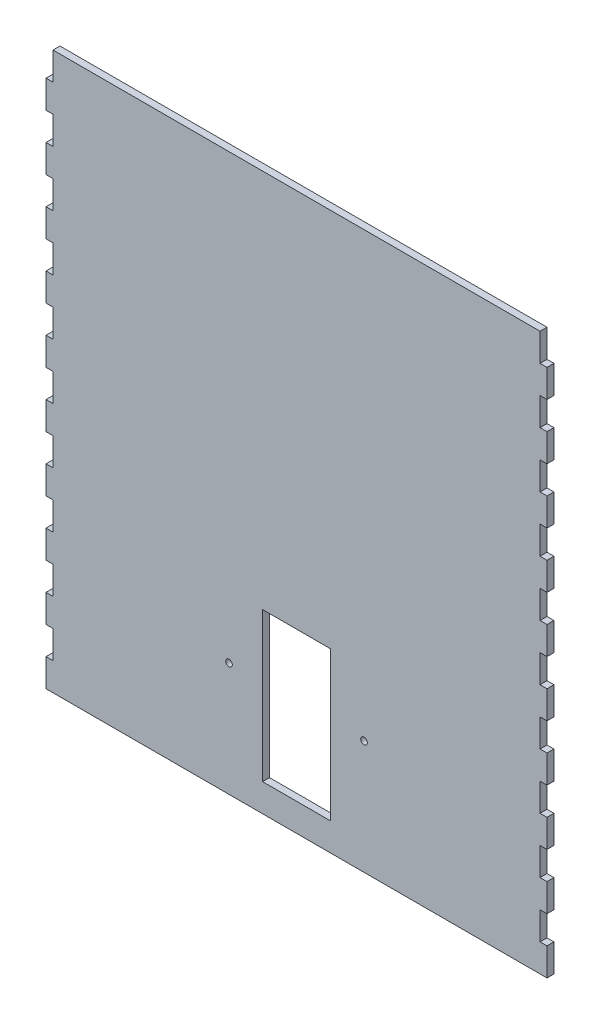
SolidWorks part; units mm, degrees
material "Acrylic (Medium-high impact)"
ref_plane "Front Plane" through (0, 0, 0) normal (0, 0, 1) x (1, 0, 0)
ref_plane "Top Plane" through (0, 0, 0) normal (0, 1, 0) x (1, 0, 0)
ref_plane "Right Plane" through (0, 0, 0) normal (1, 0, 0) x (0, 0, -1)
sketch "Sketch1" plane through (0, 0, 0) normal (0, 0, 1) x (1, 0, 0)
  line L0 (-114.3, 114.3) -> (-111.125, 114.3)
  line L1 (-114.3, 127) -> (114.3, 127)
  line L2 (-114.3, 127) -> (-114.3, -127)
  line L3 (-114.3, -127) -> (114.3, -127)
  line L4 (114.3, 127) -> (114.3, -127)
  line L5 (-114.3, 127) -> (-111.125, 127)
  line L6 (-114.3, 127) -> (-114.3, 114.3)
  line L7 (-114.3, 114.3) -> (-111.125, 114.3)
  line L8 (-111.125, 127) -> (-111.125, 114.3)
  line L9 (-114.3, 114.3) -> (-114.3, 101.6)
  line L10 (-114.3, 101.6) -> (-111.125, 101.6)
  line L11 (-111.125, 114.3) -> (-111.125, 101.6)
  line L12 (-114.3, 101.6) -> (-111.125, 101.6)
  line L13 (-114.3, 101.6) -> (-114.3, 88.9)
  line L14 (-114.3, 88.9) -> (-111.125, 88.9)
  line L15 (-111.125, 101.6) -> (-111.125, 88.9)
  line L16 (-114.3, 88.9) -> (-111.125, 88.9)
  line L17 (-114.3, 88.9) -> (-114.3, 76.2)
  line L18 (-114.3, 76.2) -> (-111.125, 76.2)
  line L19 (-111.125, 88.9) -> (-111.125, 76.2)
  line L20 (-114.3, 76.2) -> (-111.125, 76.2)
  line L21 (-114.3, 76.2) -> (-114.3, 63.5)
  line L22 (-114.3, 63.5) -> (-111.125, 63.5)
  line L23 (-111.125, 76.2) -> (-111.125, 63.5)
  line L24 (-114.3, 63.5) -> (-111.125, 63.5)
  line L25 (-114.3, 63.5) -> (-114.3, 50.8)
  line L26 (-114.3, 50.8) -> (-111.125, 50.8)
  line L27 (-111.125, 63.5) -> (-111.125, 50.8)
  line L28 (-114.3, 50.8) -> (-111.125, 50.8)
  line L29 (-114.3, 50.8) -> (-114.3, 38.1)
  line L30 (-114.3, 38.1) -> (-111.125, 38.1)
  line L31 (-111.125, 50.8) -> (-111.125, 38.1)
  line L32 (-114.3, 38.1) -> (-111.125, 38.1)
  line L33 (-114.3, 38.1) -> (-114.3, 25.4)
  line L34 (-114.3, 25.4) -> (-111.125, 25.4)
  line L35 (-111.125, 38.1) -> (-111.125, 25.4)
  line L36 (-114.3, 25.4) -> (-111.125, 25.4)
  line L37 (-114.3, 25.4) -> (-114.3, 12.7)
  line L38 (-114.3, 12.7) -> (-111.125, 12.7)
  line L39 (-111.125, 25.4) -> (-111.125, 12.7)
  line L40 (-114.3, 12.7) -> (-111.125, 12.7)
  line L41 (-114.3, 12.7) -> (-114.3, 0)
  line L42 (-114.3, 0) -> (-111.125, 0)
  line L43 (-111.125, 12.7) -> (-111.125, 0)
  line L44 (-114.3, 0) -> (-111.125, 0)
  line L45 (-114.3, 0) -> (-114.3, -12.7)
  line L46 (-114.3, -12.7) -> (-111.125, -12.7)
  line L47 (-111.125, 0) -> (-111.125, -12.7)
  line L48 (-114.3, -12.7) -> (-111.125, -12.7)
  line L49 (-114.3, -12.7) -> (-114.3, -25.4)
  line L50 (-114.3, -25.4) -> (-111.125, -25.4)
  line L51 (-111.125, -12.7) -> (-111.125, -25.4)
  line L52 (-114.3, -25.4) -> (-111.125, -25.4)
  line L53 (-114.3, -25.4) -> (-114.3, -38.1)
  line L54 (-114.3, -38.1) -> (-111.125, -38.1)
  line L55 (-111.125, -25.4) -> (-111.125, -38.1)
  line L56 (-114.3, -38.1) -> (-111.125, -38.1)
  line L57 (-114.3, -38.1) -> (-114.3, -50.8)
  line L58 (-114.3, -50.8) -> (-111.125, -50.8)
  line L59 (-111.125, -38.1) -> (-111.125, -50.8)
  line L60 (-114.3, -50.8) -> (-111.125, -50.8)
  line L61 (-114.3, -50.8) -> (-114.3, -63.5)
  line L62 (-114.3, -63.5) -> (-111.125, -63.5)
  line L63 (-111.125, -50.8) -> (-111.125, -63.5)
  line L64 (-114.3, -63.5) -> (-111.125, -63.5)
  line L65 (-114.3, -63.5) -> (-114.3, -76.2)
  line L66 (-114.3, -76.2) -> (-111.125, -76.2)
  line L67 (-111.125, -63.5) -> (-111.125, -76.2)
  line L68 (-114.3, -76.2) -> (-111.125, -76.2)
  line L69 (-114.3, -76.2) -> (-114.3, -88.9)
  line L70 (-114.3, -88.9) -> (-111.125, -88.9)
  line L71 (-111.125, -76.2) -> (-111.125, -88.9)
  line L72 (-114.3, -88.9) -> (-111.125, -88.9)
  line L73 (-114.3, -88.9) -> (-114.3, -101.6)
  line L74 (-114.3, -101.6) -> (-111.125, -101.6)
  line L75 (-111.125, -88.9) -> (-111.125, -101.6)
  line L76 (-114.3, -101.6) -> (-111.125, -101.6)
  line L77 (-114.3, -101.6) -> (-114.3, -114.3)
  line L78 (-114.3, -114.3) -> (-111.125, -114.3)
  line L79 (-111.125, -101.6) -> (-111.125, -114.3)
  line L80 (-114.3, -114.3) -> (-111.125, -114.3)
  line L81 (-114.3, -114.3) -> (-114.3, -127)
  line L82 (-114.3, -127) -> (-111.125, -127)
  line L83 (-111.125, -114.3) -> (-111.125, -127)
  line L100 (0, 127) -> (0, -127) construction
  line L101 (114.3, 114.3) -> (111.125, 114.3)
  line L102 (114.3, 127) -> (111.125, 127)
  line L103 (114.3, 127) -> (114.3, 114.3)
  line L104 (114.3, 114.3) -> (111.125, 114.3)
  line L105 (111.125, 127) -> (111.125, 114.3)
  line L106 (114.3, 114.3) -> (114.3, 101.6)
  line L107 (114.3, 101.6) -> (111.125, 101.6)
  line L108 (111.125, 114.3) -> (111.125, 101.6)
  line L109 (114.3, 101.6) -> (111.125, 101.6)
  line L110 (114.3, 101.6) -> (114.3, 88.9)
  line L111 (114.3, 88.9) -> (111.125, 88.9)
  line L112 (111.125, 101.6) -> (111.125, 88.9)
  line L113 (114.3, 88.9) -> (111.125, 88.9)
  line L114 (114.3, 88.9) -> (114.3, 76.2)
  line L115 (114.3, 76.2) -> (111.125, 76.2)
  line L116 (111.125, 88.9) -> (111.125, 76.2)
  line L117 (114.3, 76.2) -> (111.125, 76.2)
  line L118 (114.3, 76.2) -> (114.3, 63.5)
  line L119 (114.3, 63.5) -> (111.125, 63.5)
  line L120 (111.125, 76.2) -> (111.125, 63.5)
  line L121 (114.3, 63.5) -> (111.125, 63.5)
  line L122 (114.3, 63.5) -> (114.3, 50.8)
  line L123 (114.3, 50.8) -> (111.125, 50.8)
  line L124 (111.125, 63.5) -> (111.125, 50.8)
  line L125 (114.3, 50.8) -> (111.125, 50.8)
  line L126 (114.3, 50.8) -> (114.3, 38.1)
  line L127 (114.3, 38.1) -> (111.125, 38.1)
  line L128 (111.125, 50.8) -> (111.125, 38.1)
  line L129 (114.3, 38.1) -> (111.125, 38.1)
  line L130 (114.3, 38.1) -> (114.3, 25.4)
  line L131 (114.3, 25.4) -> (111.125, 25.4)
  line L132 (111.125, 38.1) -> (111.125, 25.4)
  line L133 (114.3, 25.4) -> (111.125, 25.4)
  line L134 (114.3, 25.4) -> (114.3, 12.7)
  line L135 (114.3, 12.7) -> (111.125, 12.7)
  line L136 (111.125, 25.4) -> (111.125, 12.7)
  line L137 (114.3, 12.7) -> (111.125, 12.7)
  line L138 (114.3, 12.7) -> (114.3, 0)
  line L139 (114.3, 0) -> (111.125, 0)
  line L140 (111.125, 12.7) -> (111.125, 0)
  line L141 (114.3, 0) -> (111.125, 0)
  line L142 (114.3, 0) -> (114.3, -12.7)
  line L143 (114.3, -12.7) -> (111.125, -12.7)
  line L144 (111.125, 0) -> (111.125, -12.7)
  line L145 (114.3, -12.7) -> (111.125, -12.7)
  line L146 (114.3, -12.7) -> (114.3, -25.4)
  line L147 (114.3, -25.4) -> (111.125, -25.4)
  line L148 (111.125, -12.7) -> (111.125, -25.4)
  line L149 (114.3, -25.4) -> (111.125, -25.4)
  line L150 (114.3, -25.4) -> (114.3, -38.1)
  line L151 (114.3, -38.1) -> (111.125, -38.1)
  line L152 (111.125, -25.4) -> (111.125, -38.1)
  line L153 (114.3, -38.1) -> (111.125, -38.1)
  line L154 (114.3, -38.1) -> (114.3, -50.8)
  line L155 (114.3, -50.8) -> (111.125, -50.8)
  line L156 (111.125, -38.1) -> (111.125, -50.8)
  line L157 (114.3, -50.8) -> (111.125, -50.8)
  line L158 (114.3, -50.8) -> (114.3, -63.5)
  line L159 (114.3, -63.5) -> (111.125, -63.5)
  line L160 (111.125, -50.8) -> (111.125, -63.5)
  line L161 (114.3, -63.5) -> (111.125, -63.5)
  line L162 (114.3, -63.5) -> (114.3, -76.2)
  line L163 (114.3, -76.2) -> (111.125, -76.2)
  line L164 (111.125, -63.5) -> (111.125, -76.2)
  line L165 (114.3, -76.2) -> (111.125, -76.2)
  line L166 (114.3, -76.2) -> (114.3, -88.9)
  line L167 (114.3, -88.9) -> (111.125, -88.9)
  line L168 (111.125, -76.2) -> (111.125, -88.9)
  line L169 (114.3, -88.9) -> (111.125, -88.9)
  line L170 (114.3, -88.9) -> (114.3, -101.6)
  line L171 (114.3, -101.6) -> (111.125, -101.6)
  line L172 (111.125, -88.9) -> (111.125, -101.6)
  line L173 (114.3, -101.6) -> (111.125, -101.6)
  line L174 (114.3, -101.6) -> (114.3, -114.3)
  line L175 (114.3, -114.3) -> (111.125, -114.3)
  line L176 (111.125, -101.6) -> (111.125, -114.3)
  line L177 (114.3, -114.3) -> (111.125, -114.3)
  line L178 (114.3, -114.3) -> (114.3, -127)
  line L179 (114.3, -127) -> (111.125, -127)
  line L180 (111.125, -114.3) -> (111.125, -127)
  point P4 (0, 127)
  point P6 (-114.3, 0)
  dimension "D1" = 254
  dimension "D2" = 228.6
  dimension "D3" = 12.7
  dimension "D4" = 3.175
  dimension "D5" = 20
  dimension "D6" = 20
extrude "Boss-Extrude1" add sketch "Sketch1" along normal blind 3.175
sketch "Sketch2" plane through (0, 0, 3.175) normal (0, 0, 1) x (1, 0, 0)
  line L0 (-30.8, -75.0624) -> (30.8, -75.0624) construction
  line L2 (-15.5, -46.3) -> (15.5, -46.3)
  line L3 (-15.5, -46.3) -> (-15.5, -114.3)
  line L5 (-114.3, -127) -> (114.3, -127) construction
  line L8 (-15.5, -114.3) -> (15.5, -114.3)
  line L9 (15.5, -46.3) -> (15.5, -114.3)
  circle A0 centre (-30.8, -75.0624) radius 1.5
  circle A1 centre (30.8, -75.0624) radius 1.5
  point P9 (0, -75.0624)
  point P11 (0, -127)
  point P15 (0, -114.3)
  dimension "D1" = 3
  dimension "D2" = 61.6
  dimension "D3" = 31
  dimension "D4" = 68
  dimension "D5" = 28.7624
  dimension "D6" = 12.7
extrude "Cut-Extrude1" cut sketch "Sketch2" against normal through all
